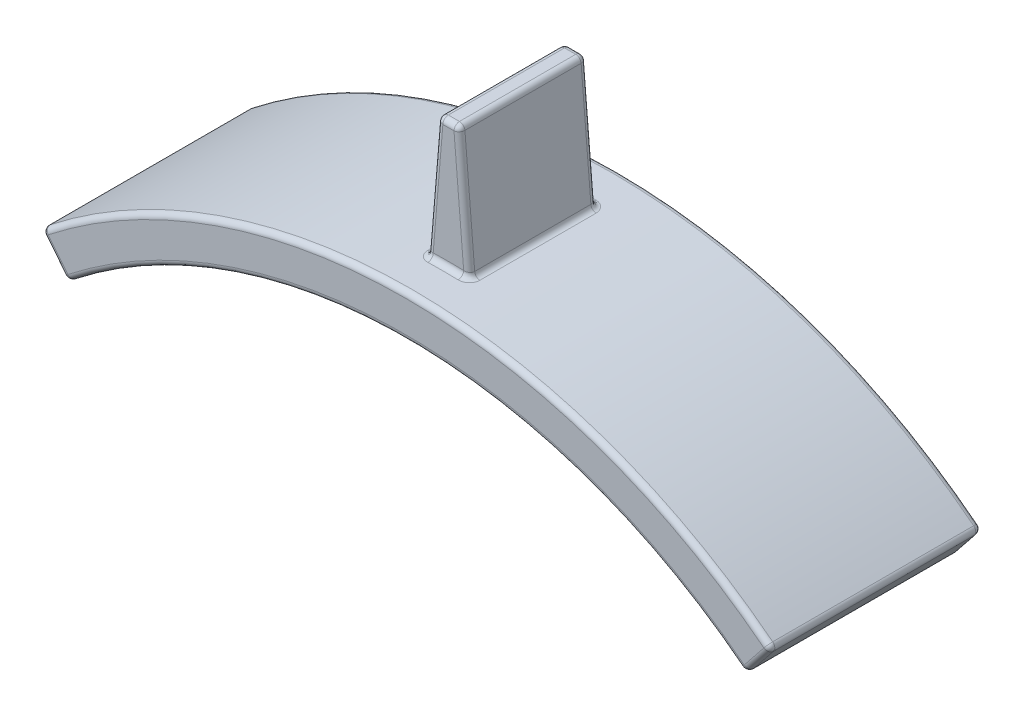
SolidWorks part; units mm, degrees
ref_plane "Front Plane" through (0, 0, 0) normal (0, 0, 1) x (1, 0, 0)
ref_plane "Top Plane" through (0, 0, 0) normal (0, 1, 0) x (1, 0, 0)
ref_plane "Right Plane" through (0, 0, 0) normal (1, 0, 0) x (0, 0, -1)
sketch "Sketch1" plane through (0, 0, 0) normal (0, 0, 1) x (1, 0, 0)
  line L0 (-13.6922, 17.1015) -> (-12.7, 15.8623)
  line L1 (13.6922, 17.1015) -> (12.7, 15.8623)
  line L2 (0, 20.32) -> (0, 26.6556) construction
  line L3 (0.7937, 21.8931) -> (0.3969, 26.6556)
  line L4 (0.3969, 26.6556) -> (0, 26.6556)
  line L5 (-0.3969, 26.6556) -> (0, 26.6556)
  line L6 (-0.7937, 21.8931) -> (-0.3969, 26.6556)
  arc A0 (-13.6922, 17.1015) -> (13.6922, 17.1015) centre (0, 0) cw
  arc A1 (-12.7, 15.8623) -> (12.7, 15.8623) centre (0, 0) cw
  arc A2 (-13.6922, 17.1015) -> (13.6922, 17.1015) centre (0, 0) cw construction
  dimension "D2" = 20.32
  dimension "D3" = 0.7937
  dimension "D4" = 1.5875
  dimension "D5" = 4.7625
  dimension "D6" = 25.4
  dimension "D1" = 1.5875
extrude "Boss-Extrude1" add sketch "Sketch1" along normal mid plane 7.9375 contours A1 L2 A0 L0 | L2 A1 L1 A0 region at (-7.5313, 20.2734, 0)
extrude "Boss-Extrude2" add sketch "Sketch1<3>" along normal mid plane 4.7625 contours L6 A0 L3 L4 L5 region at (0, 24.0155, 0)
sketch "Sketch1<3>" plane through (0, 0, 0) normal (0, 0, 1) x (1, 0, 0) same geometry as "Sketch1"
fillet "Fillet1" radius 0.2048 24 edges at (-12.7, 15.8623, 0) (0, 20.32, 3.9688) (12.7, 15.8623, 0) (0, 20.32, -3.9688) (0, 21.9075, -2.3813) (0.5953, 24.2744, -2.3812) (-0.5953, 24.2744, -2.3813) (0.5953, 24.2744, 2.3813) (0, 21.9075, 2.3813) (-0.5953, 24.2744, 2.3813) (0.3969, 26.6556, 0) (0, 26.6556, 2.3813) (-0.3969, 26.6556, 0) (0, 26.6556, -2.3813) (-13.1961, 16.4819, -3.9688) (-13.1961, 16.4819, 3.9688) (13.1961, 16.4819, -3.9688) (13.1961, 16.4819, 3.9688) (0, 21.9075, -3.9688) (0, 21.9075, 3.9688) (-0.7938, 21.8931, 0) (0.7938, 21.8931, 0) (13.6922, 17.1015, 0) (-13.6922, 17.1015, 0)
